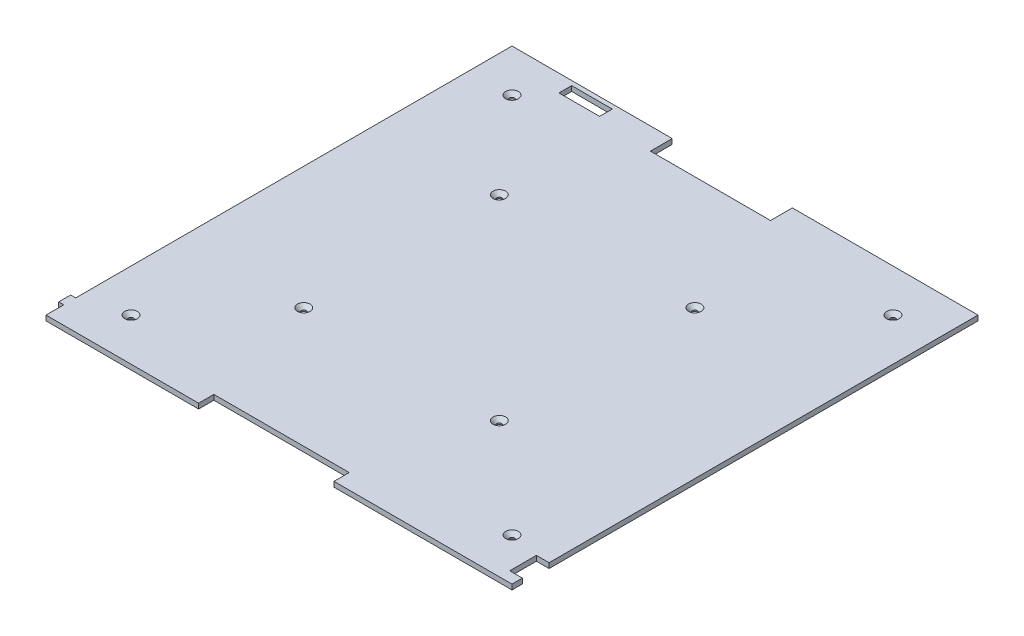
SolidWorks part; units mm, degrees
ref_plane "Front Plane" through (0, 0, 0) normal (0, 0, 1) x (1, 0, 0)
ref_plane "Top Plane" through (0, 0, 0) normal (0, 1, 0) x (1, 0, 0)
ref_plane "Right Plane" through (0, 0, 0) normal (1, 0, 0) x (0, 0, -1)
sketch "Sketch1" plane through (0, 0, 0) normal (0, 1, 0) x (1, 0, 0)
  line L0 (-92, 92) -> (-92, -79.8) construction
  line L1 (-28.4, 92) -> (-92, 92) construction
  line L2 (-28.4, 83.4) -> (-28.4, 92) construction
  line L3 (18.4, 83.4) -> (-28.4, 83.4) construction
  line L4 (18.4, 92) -> (18.4, 83.4) construction
  line L5 (92, 92) -> (18.4, 92) construction
  line L6 (92, -77.4) -> (92, 92) construction
  line L7 (87, -77.4) -> (92, -77.4) construction
  line L8 (87, -87.4) -> (87, -77.4) construction
  line L9 (92, -87.4) -> (87, -87.4) construction
  line L10 (92, -92) -> (92, -87.4) construction
  line L11 (21.4, -92) -> (92, -92) construction
  line L12 (21.4, -86) -> (21.4, -92) construction
  line L13 (-31.4, -86) -> (21.4, -86) construction
  line L14 (-31.4, -92) -> (-31.4, -86) construction
  line L15 (-92, -92) -> (-31.4, -92) construction
  line L16 (-92, -85) -> (-92, -92) construction
  line L17 (-94, -85) -> (-92, -85) construction
  line L18 (-94, -79.8) -> (-94, -85) construction
  line L19 (-92, -79.8) -> (-94, -79.8) construction
  line L20 (-91.75, 91.75) -> (-91.75, -80.05)
  line L21 (-91.75, -80.05) -> (-93.75, -80.05)
  line L22 (-93.75, -80.05) -> (-93.75, -84.75)
  line L23 (-93.75, -84.75) -> (-91.75, -84.75)
  line L24 (-91.75, -84.75) -> (-91.75, -91.75)
  line L25 (-91.75, -91.75) -> (-31.65, -91.75)
  line L26 (-31.65, -91.75) -> (-31.65, -85.75)
  line L27 (-31.65, -85.75) -> (21.65, -85.75)
  line L28 (21.65, -85.75) -> (21.65, -91.75)
  line L29 (21.65, -91.75) -> (91.75, -91.75)
  line L30 (91.75, -91.75) -> (91.75, -87.65)
  line L31 (91.75, -87.65) -> (86.75, -87.65)
  line L32 (86.75, -87.65) -> (86.75, -77.15)
  line L33 (86.75, -77.15) -> (91.75, -77.15)
  line L34 (91.75, -77.15) -> (91.75, 91.75)
  line L35 (91.75, 91.75) -> (18.65, 91.75)
  line L36 (18.65, 91.75) -> (18.65, 83.15)
  line L37 (18.65, 83.15) -> (-28.65, 83.15)
  line L38 (-28.65, 83.15) -> (-28.65, 91.75)
  line L39 (-28.65, 91.75) -> (-91.75, 91.75)
  dimension "D1" = 184
  dimension "D2" = 184
  dimension "D3" = 8.6
  dimension "D4" = 63.6
  dimension "D5" = 46.8
  dimension "D6" = 2
  dimension "D7" = 7
  dimension "D8" = 5.2
  dimension "D9" = 4.6
  dimension "D10" = 10
  dimension "D11" = 70.6
  dimension "D12" = 52.8
  dimension "D13" = 5
  dimension "D14" = 6
  dimension "D15" = 92
  dimension "D16" = 92
  dimension "D17" = 0.25
extrude "Boss-Extrude1" add sketch "Sketch1" along normal blind 2
sketch "Sketch2" plane through (0, 0, 0) normal (0, -1, 0) x (1, 0, 0)
  circle A0 centre (75, -75) radius 1
  circle A1 centre (-75, -75) radius 1
  circle A2 centre (-75, 75) radius 1
  circle A3 centre (75, 75) radius 1
  circle A4 centre (33.5, -38.5) radius 1
  circle A5 centre (33.5, 38.5) radius 1
  circle A6 centre (-43.5, -38.5) radius 1
  circle A7 centre (-43.5, 38.5) radius 1
  dimension "D1" = 2
  dimension "D2" = 2
  dimension "D3" = 2
  dimension "D4" = 2
  dimension "D5" = 2
  dimension "D6" = 2
  dimension "D7" = 2
  dimension "D8" = 2
extrude "Cut-Extrude1" cut sketch "Sketch2" against normal through all
chamfer "Chamfer1" distance 1.5 angle 45 8 edges at (75, 2, -76) (33.5, 2, -39.5) (75, 2, 74) (33.5, 2, 37.5) (-43.5, 2, 37.5) (-43.5, 2, -39.5) (-75, 2, -76) (-75, 2, 74)
sketch "Sketch3" plane through (0, 0, 0) normal (0, -1, 0) x (1, 0, 0)
  line L1 (-50.5, -90) -> (-66.5, -90)
  line L2 (-50.5, -90) -> (-50.5, -85)
  line L3 (-50.5, -85) -> (-66.5, -85)
  line L4 (-66.5, -90) -> (-66.5, -85)
extrude "Cut-Extrude2" cut sketch "Sketch3" against normal through all
sketch "Sketch4" plane through (0, 0, 0) normal (0, -1, 0) x (1, 0, 0)
  line L0 (-28.65, -91.75) -> (-91.75, -91.75) construction
  line L1 (-47.4296, -19.75) -> (-39.8007, -19.75)
  line L2 (-47.4296, -19.75) -> (-47.4296, 20.25)
  line L3 (-47.4296, 20.25) -> (-39.8007, 20.25)
  line L4 (-39.8007, -19.75) -> (-39.8007, 20.25)
  line L5 (-91.75, -91.75) -> (-91.75, 80.05) construction
  dimension "D1" = 72
  dimension "D2" = 7.6289
  dimension "D3" = 44.3204
  dimension "D4" = 40
extrude "Cut-Extrude3" cut sketch "Sketch4" against normal blind 1.4
